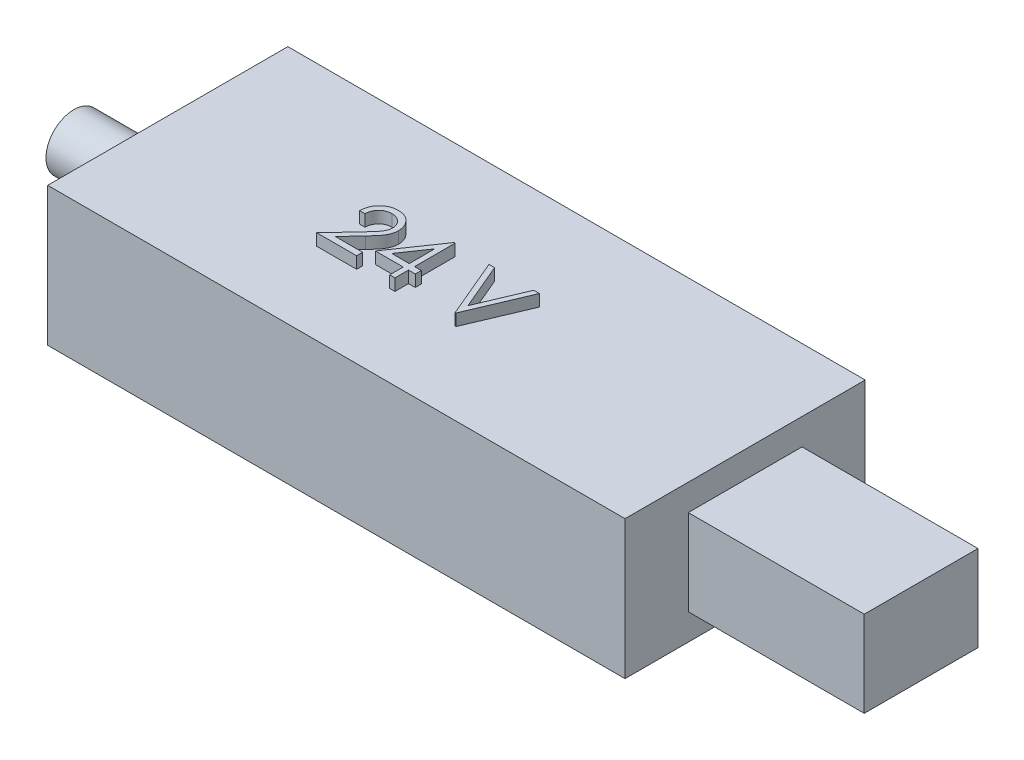
SolidWorks part; units mm, degrees
ref_plane "Front Plane" through (0, 0, 0) normal (0, 0, 1) x (1, 0, 0)
ref_plane "Top Plane" through (0, 0, 0) normal (0, 1, 0) x (1, 0, 0)
ref_plane "Right Plane" through (0, 0, 0) normal (1, 0, 0) x (0, 0, -1)
sketch "Sketch1" plane through (0, 0, 0) normal (0, 1, 0) x (1, 0, 0)
  line L1 (-62.5, 26) -> (62.5, 26)
  line L2 (-62.5, 26) -> (-62.5, -26)
  line L3 (-62.5, -26) -> (62.5, -26)
  line L4 (62.5, 26) -> (62.5, -26)
  line L5 (-62.5, 26) -> (62.5, -26) construction
  line L6 (-62.5, -26) -> (62.5, 26) construction
  point P0 (0, 0)
  dimension "D1" = 125
  dimension "D2" = 52
extrude "Boss-Extrude1" add sketch "Sketch1" along normal blind 30
sketch "Sketch2" plane through (62.5, 0, 0) normal (1, 0, 0) x (0, 0, -1)
  line L0 (-26, 15) -> (26, 15) construction
  line L1 (-26, 30) -> (-26, 0) construction
  line L2 (26, 30) -> (26, 0) construction
  line L4 (-12.3134, 24.2992) -> (12.3134, 24.2992)
  line L5 (-12.3134, 24.2992) -> (-12.3134, 5.7008)
  line L6 (-12.3134, 5.7008) -> (12.3134, 5.7008)
  line L7 (12.3134, 24.2992) -> (12.3134, 5.7008)
  line L8 (-12.3134, 24.2992) -> (12.3134, 5.7008) construction
  line L9 (-12.3134, 5.7008) -> (12.3134, 24.2992) construction
  point P6 (0, 15)
extrude "Boss-Extrude2" add sketch "Sketch2" along normal blind 38.1
sketch "Sketch3" plane through (-62.5, 0, 0) normal (-1, 0, 0) x (0, 0, 1)
  line L0 (-26, 15) -> (26, 15) construction
  line L1 (-26, 30) -> (-26, 0) construction
  line L2 (26, 30) -> (26, 0) construction
  circle A0 centre (0, 15) radius 6.0394
extrude "Boss-Extrude3" add sketch "Sketch3" along normal blind 20.32
sketch "Sketch4" plane through (0, 30, 0) normal (0, 1, 0) x (1, 0, 0)
  text T0 "24 V" font "Century Gothic" height 12.7
extrude "Boss-Extrude4" add sketch "Sketch4" along normal blind 2.54
